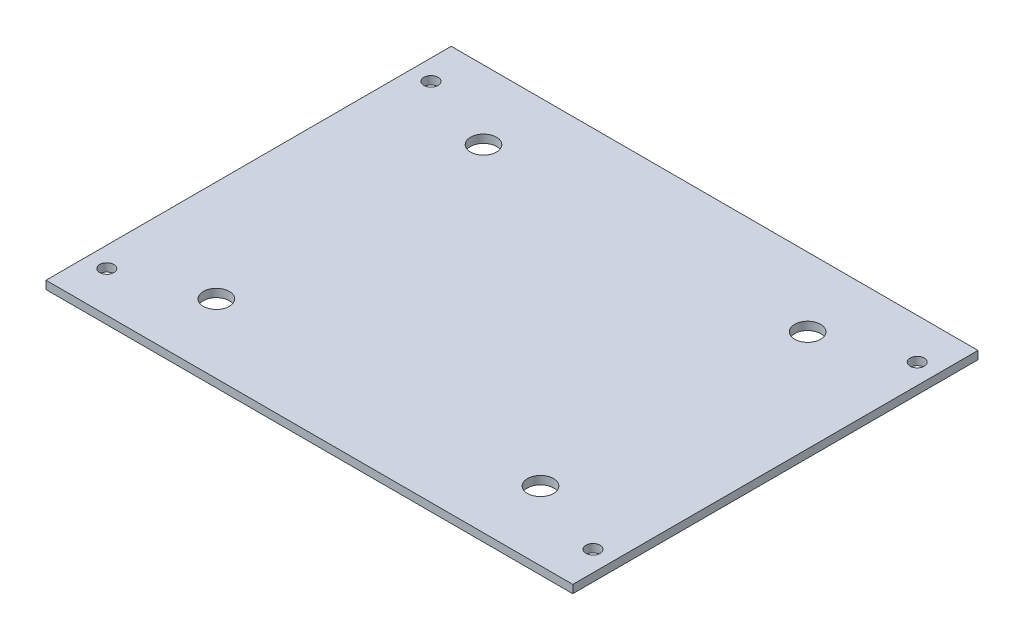
SolidWorks part; units mm, degrees
material "1060 Сплав"
ref_plane "Спереди" through (0, 0, 0) normal (0, 0, 1) x (1, 0, 0)
ref_plane "Сверху" through (0, 0, 0) normal (0, 1, 0) x (1, 0, 0)
ref_plane "Справа" through (0, 0, 0) normal (1, 0, 0) x (0, 0, -1)
sketch "Эскиз1" plane through (0, 0, 0) normal (0, 1, 0) x (1, 0, 0)
  line L0 (105, 17.0342) -> (25, 17.0342) construction
  line L5 (0, 0) -> (130, 0)
  line L6 (0, 0) -> (0, 100)
  line L7 (0, 100) -> (130, 100)
  line L8 (130, 0) -> (130, 100)
  line L9 (130, 50) -> (0, 50) construction
  line L10 (65, 100) -> (65, 0) construction
  circle A0 centre (105, 17.0342) radius 3.2
  circle A1 centre (25, 17.0342) radius 3.2
  circle A2 centre (105, 82.9658) radius 3.2
  circle A3 centre (25, 82.9658) radius 3.2
  circle A4 centre (5, 90) radius 1.75
  circle A5 centre (5, 10) radius 1.75
  circle A6 centre (125, 10) radius 1.75
  circle A7 centre (125, 90) radius 1.75
  dimension "D3" = 3.5
  dimension "D1" = 130
  dimension "D2" = 100
  dimension "D4" = 10
  dimension "D5" = 5
extrude "Бобышка-Вытянуть1" add sketch "Эскиз1" along normal blind 2
